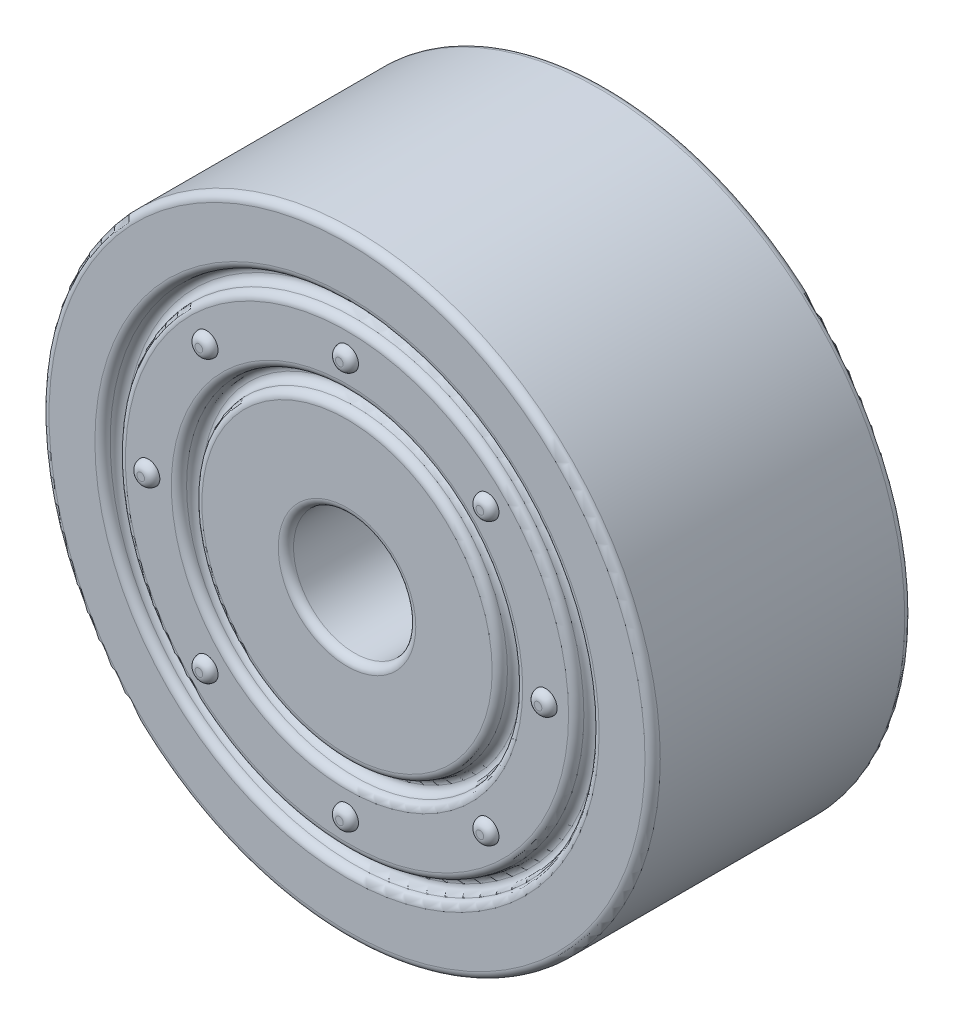
SolidWorks part; units mm, degrees
material "Stainless Steel (ferritic)"
ref_plane "Front" through (0, 0, 0) normal (0, 0, 1) x (1, 0, 0)
ref_plane "Top" through (0, 0, 0) normal (0, 1, 0) x (1, 0, 0)
ref_plane "Right" through (0, 0, 0) normal (1, 0, 0) x (0, 0, -1)
sketch "Sketch1" plane through (0, 0, 0) normal (0, 0, 1) x (1, 0, 0)
  circle A0 centre (0, 0) radius 20
  circle A1 centre (0, 0) radius 4
extrude "Boss-Extrude2" add sketch "Sketch1" along normal blind 17
sketch "Sketch3" plane through (0, 0, 17) normal (0, 0, 1) x (1, 0, 0)
  circle A0 centre (0, 0) radius 16
  circle A1 centre (0, 0) radius 15
extrude "Cut-Extrude1" cut sketch "Sketch3" against normal blind 1
fillet "Fillet9" radius 0.5 2 edges at (15, 0, 16) (16, 0, 16)
fillet "Fillet10" radius 0.5 2 edges at (16, 0, 17) (15, 0, 17)
sketch "Sketch4" plane through (0, 0, 17) normal (0, 0, 1) x (1, 0, 0)
  circle A0 centre (0, 0) radius 11
  circle A1 centre (0, 0) radius 10
extrude "Cut-Extrude2" cut sketch "Sketch4" against normal blind 1
fillet "Fillet11" radius 0.5 4 edges at (10, 0, 16) (11, 0, 16) (11, 0, 17) (10, 0, 17)
fillet "Fillet12" radius 0.5 2 edges at (20, 0, 0) (20, 0, 17)
sketch "Sketch6" plane through (0, 0, 17) normal (0, 0, 1) x (1, 0, 0)
  circle A0 centre (0, 0) radius 13 construction
  circle A1 centre (0, 13) radius 0.75
  circle A2 centre (9.1924, 9.1924) radius 0.75
  circle A3 centre (13, 0) radius 0.75
  circle A4 centre (9.1924, -9.1924) radius 0.75
  circle A5 centre (0, -13) radius 0.75
  circle A6 centre (-9.1924, -9.1924) radius 0.75
  circle A7 centre (-13, 0) radius 0.75
  circle A8 centre (-9.1924, 9.1924) radius 0.75
  point P22 (0, 0)
  dimension "D1" = 8
extrude "Boss-Extrude5" add sketch "Sketch6" along normal blind 0.5
fillet "Fillet17" radius 0.5 2 edges at (4, 0, 0) (4, 0, 17)
fillet "Fillet18" radius 0.5 1 edges at (9.9424, -9.1924, 17.5)
fillet "Fillet19" radius 0.5 1 edges at (0.75, -13, 17.5)
fillet "Fillet20" radius 0.5 6 edges at (13.75, 0, 17.5) (9.9424, 9.1924, 17.5) (0.75, 13, 17.5) (-8.4424, 9.1924, 17.5) (-12.25, 0, 17.5) (-8.4424, -9.1924, 17.5)
